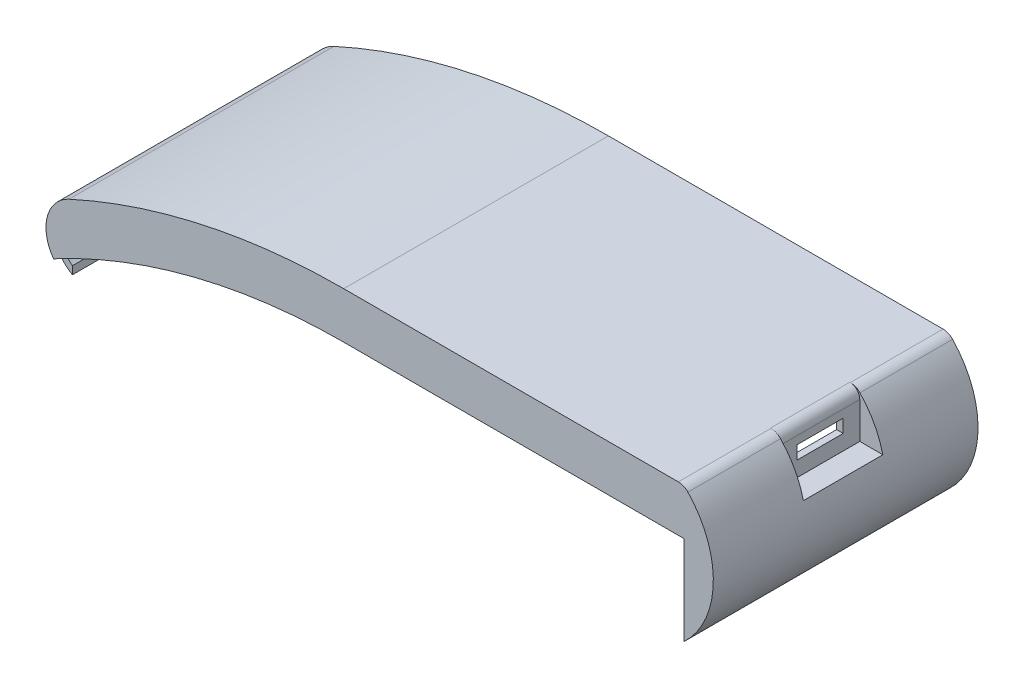
SolidWorks part; units mm, degrees
ref_plane "Front Plane" through (0, 0, 0) normal (0, 0, 1) x (1, 0, 0)
ref_plane "Top Plane" through (0, 0, 0) normal (0, 1, 0) x (1, 0, 0)
ref_plane "Right Plane" through (0, 0, 0) normal (1, 0, 0) x (0, 0, -1)
sketch "Sketch1" plane through (0, 0, 0) normal (0, 0, 1) x (1, 0, 0)
  line L0 (93.6716, -39.9694) -> (93.6716, -40.9694)
  line L1 (3.6716, -40.9694) -> (3.6716, -39.9694)
  line L2 (3.6716, -39.9694) -> (-32.9868, -39.9694) construction
  line L3 (93.6716, -40.9694) -> (94.0742, -40.9694)
  line L4 (93.6271, -20.4794) -> (94.053, -20.4794)
  line L7 (93.6516, -21.4794) -> (42.6716, -21.4794)
  line L8 (93.6482, -40.9694) -> (93.6716, -40.9694)
  line L9 (93.6271, -20.4794) -> (42.6716, -20.4794)
  line L17 (93.6482, -40.9694) -> (3.6716, -40.9694) construction
  line L19 (93.6716, -39.9694) -> (3.6716, -39.9694) construction
  arc A0 (93.6516, -21.4794) -> (93.6716, -39.9694) centre (94.1163, -30.7239) cw construction
  arc A1 (42.6716, -21.4794) -> (1.5932, -30.4219) centre (42.6716, -120.3004) ccw
  arc A2 (1.5932, -30.4219) -> (3.6716, -39.9694) centre (3.6716, -34.9694) ccw
  arc A3 (93.6271, -20.4794) -> (93.6482, -40.9694) centre (94.1163, -30.7239) cw construction
  arc A4 (1.1775, -29.5124) -> (3.6716, -40.9694) centre (3.6716, -34.9694) ccw
  arc A5 (42.6716, -20.4794) -> (1.1775, -29.5124) centre (42.6716, -120.3004) ccw
  arc A6 (93.6516, -21.4794) -> (93.6716, -39.9694) centre (94.1163, -30.7239) cw construction
  arc A7 (93.6716, -39.9694) -> (93.6516, -21.4794) centre (84.5221, -30.7343) ccw
  arc A8 (94.0742, -40.9694) -> (94.053, -20.4794) centre (84.5221, -30.7343) ccw
  arc A9 (94.3754, -40.6798) -> (94.3539, -20.7675) centre (84.5221, -30.7343) ccw construction
  point P12 (0, 0)
  point P13 (0, 0)
  point P17 (94.1163, -20.7675)
  point P28 (94.3754, -20.7675)
  point P29 (94.1163, -20.7675)
  point P30 (0, 0)
  point P31 (0, 0)
  dimension "D9" = 5
  dimension "D6" = 13
  dimension "D2" = 1
  dimension "D3" = 50.98
  dimension "D4" = 19.49
  dimension "D5" = 90
  dimension "D7" = 1
  dimension "D8" = 39
  dimension "D1" = 1
extrude "Boss-Extrude1" add sketch "Sketch1" along normal blind 38 contours L9 A5 A4 A2 A1 L7 A0 L8 A3 region at (97.6251, -30.7201, 0)
sketch "Sketch2" plane through (0, 0, 0) normal (0, 0, -1) x (-1, 0, 0)
  line L0 (-93.6716, -40.9694) -> (-3.6716, -40.9694)
  line L6 (-93.6716, -40.9694) -> (-93.6716, -39.9694)
  line L7 (-94.0742, -40.9694) -> (-93.6716, -40.9694)
  line L8 (-42.6716, -20.4794) -> (-94.053, -20.4794)
  line L9 (-94.0742, -40.9694) -> (-93.6716, -40.9694)
  line L10 (-3.6716, -39.9694) -> (-3.6716, -40.9694)
  line L12 (-93.6516, -21.4794) -> (-42.6716, -21.4794)
  line L16 (-42.6716, -20.4794) -> (-94.053, -20.4794)
  arc A6 (-93.6516, -21.4794) -> (-93.6716, -39.9694) centre (-84.5221, -30.7343) ccw
  arc A8 (-1.5932, -30.4219) -> (-42.6716, -21.4794) centre (-42.6716, -120.3004) ccw
  arc A9 (-3.6716, -39.9694) -> (-1.5932, -30.4219) centre (-3.6716, -34.9694) ccw
  arc A10 (-3.6716, -40.9694) -> (-1.1775, -29.5124) centre (-3.6716, -34.9694) ccw
  arc A11 (-1.1775, -29.5124) -> (-42.6716, -20.4794) centre (-42.6716, -120.3004) ccw
  arc A12 (-94.053, -20.4794) -> (-94.0742, -40.9694) centre (-84.5221, -30.7343) ccw
  arc A13 (-94.053, -20.4794) -> (-94.0742, -40.9694) centre (-84.5221, -30.7343) ccw
  arc A16 (-3.6716, -40.9694) -> (-1.1775, -29.5124) centre (-3.6716, -34.9694) ccw
  arc A17 (-1.1775, -29.5124) -> (-42.6716, -20.4794) centre (-42.6716, -120.3004) ccw
  point P2 (10.0223, -4.3224)
  dimension "D1" = 0
extrude "Boss-Extrude2" add sketch "Sketch2" along normal blind 1
ref_plane "Plane1" through (0, 0, 19) normal (0, 0, 1) x (1, 0, 0)
mirror "Mirror1" about plane through (0, 0, 19) normal (0, 0, 1) of "Boss-Extrude2"
sketch "Sketch5" plane through (0, -21.4794, 0) normal (0, -1, 0) x (1, 0, 0)
  line L0 (42.6716, 38) -> (42.6716, 0) construction
  line L1 (45.3016, 27.89) -> (45.3016, 10.11) construction
  circle A0 centre (45.3016, 27.89) radius 1.5
  circle A1 centre (45.3016, 10.11) radius 1.5
  circle A2 centre (91.0216, 27.89) radius 1.5
  circle A3 centre (91.0216, 10.11) radius 1.5
  point P6 (42.6716, 19)
  point P7 (45.3016, 19)
  dimension "D3" = 3
  dimension "D1" = 2.63
  dimension "D2" = 17.78
  dimension "D4" = 2
extrude "Boss-Extrude4" add sketch "Sketch5" along normal blind 2
sketch "Sketch6" plane through (0.0001, -40.9694, 0) normal (0, -1, 0) x (1, 0, 0)
  line L0 (3.6715, 38) -> (3.6715, 0) construction
  line L2 (3.6715, 31.5) -> (-0.3285, 31.5)
  line L3 (3.6715, 31.5) -> (3.6715, 6.5)
  line L4 (3.6715, 6.5) -> (-0.3285, 6.5)
  line L5 (-0.3285, 31.5) -> (-0.3285, 6.5)
  point P6 (3.6715, 19)
  point P7 (-0.3285, 19)
  dimension "D1" = 25
  dimension "D2" = 4
extrude "Cut-Extrude1" cut sketch "Sketch6" against normal up to next
ref_plane "Plane2" through (98.5221, 0, 0) normal (1, 0, 0) x (0, 0, -1)
sketch "Sketch7" plane through (98.5221, 0, 0) normal (1, 0, 0) x (0, 0, -1)
  line L1 (-25, -20.4794) -> (-13, -20.4794)
  line L2 (-25, -20.4794) -> (-25, -27.4794)
  line L3 (-25, -27.4794) -> (-13, -27.4794)
  line L4 (-13, -20.4794) -> (-13, -27.4794)
  line L5 (-39, -20.4794) -> (1, -20.4794) construction
  point P7 (-19, -20.4794)
  dimension "D1" = 12
  dimension "D2" = 7
extrude "Cut-Extrude2" cut sketch "Sketch7" against normal up to vertex (4.8705 mm away) up to point (93.6516, -21.4794, 0)
sketch "Sketch8" plane through (93.6516, 0, 0) normal (1, 0, 0) x (0, 0, -1)
  line L0 (-13, -27.4794) -> (-25, -27.4794) construction
  line L1 (-13, -20.4794) -> (-13, -27.4794) construction
  line L2 (-25, -27.4794) -> (-25, -20.4794) construction
  line L3 (-13, -20.4794) -> (-13, -27.4794) construction
  line L4 (-25, -27.4794) -> (-25, -20.4794) construction
  line L5 (-25, -27.4794) -> (-13, -27.4794) construction
  line L6 (-12, -20.4794) -> (-12, -28.4794)
  line L7 (-26, -28.4794) -> (-12, -28.4794)
  line L8 (-26, -28.4794) -> (-26, -20.4794)
  line L9 (-26, -20.4794) -> (-12, -20.4794)
  line L11 (-22.5, -23.1794) -> (-15.5, -23.1794)
  line L12 (-22.5, -23.1794) -> (-22.5, -25.1794)
  line L13 (-22.5, -25.1794) -> (-15.5, -25.1794)
  line L14 (-15.5, -23.1794) -> (-15.5, -25.1794)
  line L15 (-13, -20.4794) -> (1, -20.4794) construction
  point P12 (-19, -23.1794)
  point P13 (-19, -20.4794)
  dimension "D2" = 7
  dimension "D3" = 2
  dimension "D4" = 2.7
  dimension "D1" = 1
extrude "Boss-Extrude5" add sketch "Sketch8" along normal blind 1
sketch "Sketch9" plane through (0, 0, 26) normal (0, 0, 1) x (1, 0, 0)
  line L2 (94.6516, -21.0702) -> (94.6516, -20.4794)
  line L3 (94.6516, -20.4794) -> (94.053, -20.4794)
  line L4 (94.6516, -21.0702) -> (94.6516, -20.4794)
  line L5 (94.6516, -20.4794) -> (94.053, -20.4794)
  arc A1 (94.6516, -21.0702) -> (94.053, -20.4794) centre (84.5221, -30.7343) ccw
  arc A2 (94.6516, -21.0702) -> (94.053, -20.4794) centre (84.5221, -30.7343) ccw
  dimension "D1" = 0
extrude "Cut-Extrude3" cut sketch "Sketch9" against normal up to next
sketch "Sketch10" plane through (94.6516, 0, 0) normal (1, 0, 0) x (0, 0, -1)
  line L0 (-26, -22.586) -> (-26, -28.4794) construction
  line L1 (-26, -28.4794) -> (-12, -28.4794) construction
  line L2 (-12, -28.4794) -> (-12, -22.586) construction
  line L3 (-26, -22.586) -> (-26, -28.4794)
  line L4 (-26, -28.4794) -> (-12, -28.4794)
  line L5 (-12, -28.4794) -> (-12, -22.586)
  line L6 (-25, -22.586) -> (-25, -27.4794)
  line L7 (-25, -27.4794) -> (-13, -27.4794)
  line L8 (-13, -27.4794) -> (-13, -22.586)
  line L9 (-26, -22.586) -> (-25, -22.586)
  line L10 (-12, -22.586) -> (-13, -22.586)
  dimension "D1" = 1
extrude "Boss-Extrude6" add sketch "Sketch10" along normal up to next
fillet "Fillet1" radius 2 1 edges at (94.053, -20.4794, 19)
fillet "Fillet2" radius 1.5 2 edges at (93.6516, -28.4794, 19) (94.6516, -21.0709, 19)
sketch "Sketch11" plane through (0, 0, 39) normal (0, 0, 1) x (1, 0, 0)
  line L1 (94.0742, -40.9694) -> (94.0742, -27.4794)
  line L2 (42.6716, -27.4794) -> (93.2317, -27.4794)
  line L3 (42.6716, -27.4794) -> (94.0742, -27.4794)
  line L4 (94.0742, -40.9694) -> (3.6716, -40.9694) construction
  line L5 (94.0742, -40.9694) -> (3.6716, -40.9694)
  arc A1 (1.1775, -29.5124) -> (3.6716, -40.9694) centre (3.6716, -34.9694) ccw construction
  arc A2 (42.6716, -27.4794) -> (4.0873, -35.8789) centre (42.6716, -120.3004) ccw
  arc A3 (42.6716, -27.4794) -> (-1.1844, -38.4934) centre (42.6716, -120.3004) ccw
  arc A4 (-1.1844, -38.4934) -> (3.6716, -40.9694) centre (3.6716, -34.9694) ccw
  point P2 (94.7676, -27.4794)
  point P7 (-1.1843, -38.4936)
  dimension "D1" = 7
extrude "Cut-Extrude4" cut sketch "Sketch11" against normal up to surface (1 mm away) up to face at (47.448, -33.4117, 38)
sketch "Sketch12" plane through (0, 0, 38) normal (0, 0, 1) x (1, 0, 0)
  line L0 (0.6716, -40.1656) -> (0.6716, -38.9694)
  line L1 (3.6716, -40.9694) -> (3.6716, -39.9694)
  line L2 (3.6716, -40.9694) -> (3.6716, -39.9694)
  line L3 (-0.3284, -37.9694) -> (-0.3284, -39.4415) construction
  arc A3 (-0.2899, -38.0201) -> (3.6716, -39.9694) centre (3.6716, -34.9694) ccw
  arc A4 (-0.2899, -38.0201) -> (-1.1844, -38.4934) centre (42.6716, -120.3004) ccw
  arc A5 (-1.1844, -38.4934) -> (3.6716, -40.9694) centre (3.6716, -34.9694) ccw
  arc A6 (0.6716, -38.9694) -> (3.6716, -39.9694) centre (3.6716, -34.9694) ccw
  arc A8 (0.6716, -40.1656) -> (3.6716, -40.9694) centre (3.6716, -34.9694) ccw
  dimension "D2" = 1
  dimension "D1" = 0
extrude "Cut-Extrude5" cut sketch "Sketch12" against normal through all both and the other way through all
sketch "Sketch13" plane through (0, 0, -1) normal (0, 0, -1) x (-1, 0, 0)
  line L0 (-94.0742, -27.4794) -> (-94.0742, -39.5523) construction
  line L1 (-42.6716, -27.4794) -> (-94.0742, -27.4794) construction
  line L2 (-94.0742, -27.4794) -> (-94.0742, -40.9694)
  line L3 (-42.6716, -27.4794) -> (-94.0742, -27.4794)
  line L4 (-94.0742, -40.9694) -> (-3.6716, -40.9694) construction
  line L6 (-3.6716, -40.9694) -> (-3.6716, -39.9694) construction
  line L7 (-3.6716, -40.9694) -> (-3.6716, -39.9694)
  line L8 (-94.0742, -40.9694) -> (-3.6716, -40.9694)
  line L9 (-0.6716, -38.9694) -> (-0.6716, -40.1656) construction
  line L10 (-0.6716, -38.9694) -> (-0.6716, -40.1656)
  arc A0 (0.2899, -38.0201) -> (-42.6716, -27.4794) centre (-42.6716, -120.3004) ccw construction
  arc A1 (1.1844, -38.4934) -> (-42.6716, -27.4794) centre (-42.6716, -120.3004) ccw
  arc A2 (-0.6716, -40.1656) -> (-1.1775, -29.5124) centre (-3.6716, -34.9694) ccw construction
  arc A3 (-3.6716, -39.9694) -> (-0.6716, -38.9694) centre (-3.6716, -34.9694) ccw construction
  arc A4 (-3.6716, -39.9694) -> (-0.6716, -38.9694) centre (-3.6716, -34.9694) ccw
  arc A5 (-0.6716, -40.1656) -> (1.1844, -38.4934) centre (-3.6716, -34.9694) ccw
  point P5 (1.1848, -38.4929)
  point P10 (-94.0742, -40.9694)
extrude "Cut-Extrude6" cut sketch "Sketch13" against normal up to surface (1 mm away) up to face at (41.7676, -33.9994, 0)
